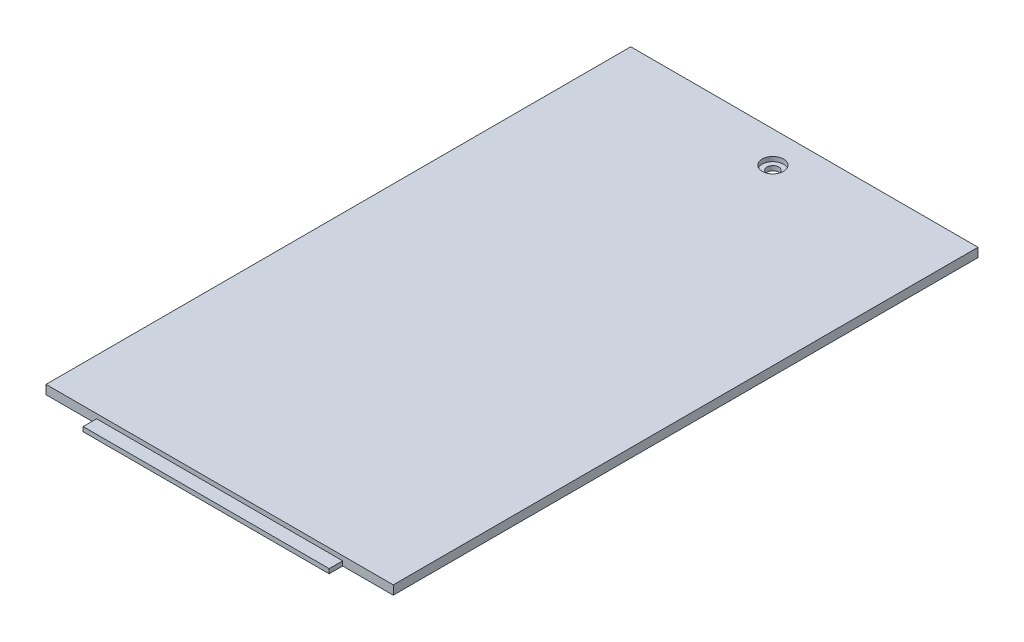
SolidWorks part; units mm, degrees
material "PLA"
ref_plane "Спереди" through (0, 0, 0) normal (0, 0, 1) x (1, 0, 0)
ref_plane "Сверху" through (0, 0, 0) normal (0, 1, 0) x (1, 0, 0)
ref_plane "Справа" through (0, 0, 0) normal (1, 0, 0) x (0, 0, -1)
sketch "Эскиз1" plane through (0, 0, 0) normal (0, 1, 0) x (1, 0, 0)
  line L1 (38.6, 65) -> (-38.6, 65)
  line L2 (38.6, 65) -> (38.6, -65)
  line L3 (38.6, -65) -> (-38.6, -65)
  line L4 (-38.6, 65) -> (-38.6, -65)
  line L5 (38.6, 65) -> (-38.6, -65) construction
  line L6 (38.6, -65) -> (-38.6, 65) construction
  point P0 (0, 0)
  dimension "D1" = 77.2
  dimension "D2" = 130
extrude "Бобышка-Вытянуть1" add sketch "Эскиз1" along normal blind 2
sketch "Эскиз3" plane through (0, 2, 0) normal (0, 1, 0) x (1, 0, 0)
  line L0 (0, 0) -> (0, 50000) construction
  line L1 (38.6, 65) -> (-38.6, 65) construction
  circle A0 centre (0, 58) radius 1.3
  dimension "D1" = 2.6
  dimension "D2" = 7
extrude "Вырез-Вытянуть1" cut sketch "Эскиз3" against normal through all
sketch "Эскиз5" plane through (0, 2, 0) normal (0, 1, 0) x (1, 0, 0)
  circle A0 centre (0, 58) radius 2.375
  dimension "D1" = 4.75
extrude "Вырез-Вытянуть2" cut sketch "Эскиз5" against normal blind 1
sketch "Эскиз6" plane through (0, 0, 65) normal (0, 0, 1) x (1, 0, 0)
  line L0 (0, 0) -> (0, 50000) construction
  line L1 (-38.6, 0) -> (38.6, 0) construction
  line L3 (27.35, 1) -> (-27.35, 1)
  line L4 (27.35, 1) -> (27.35, 0)
  line L5 (27.35, 0) -> (-27.35, 0)
  line L6 (-27.35, 1) -> (-27.35, 0)
  line L7 (27.35, 1) -> (-27.35, 0) construction
  line L8 (27.35, 0) -> (-27.35, 1) construction
  point P4 (0, 0)
  point P5 (0, 0.5)
  dimension "D1" = 54.7
  dimension "D2" = 1
extrude "Бобышка-Вытянуть2" add sketch "Эскиз6" along normal blind 3
